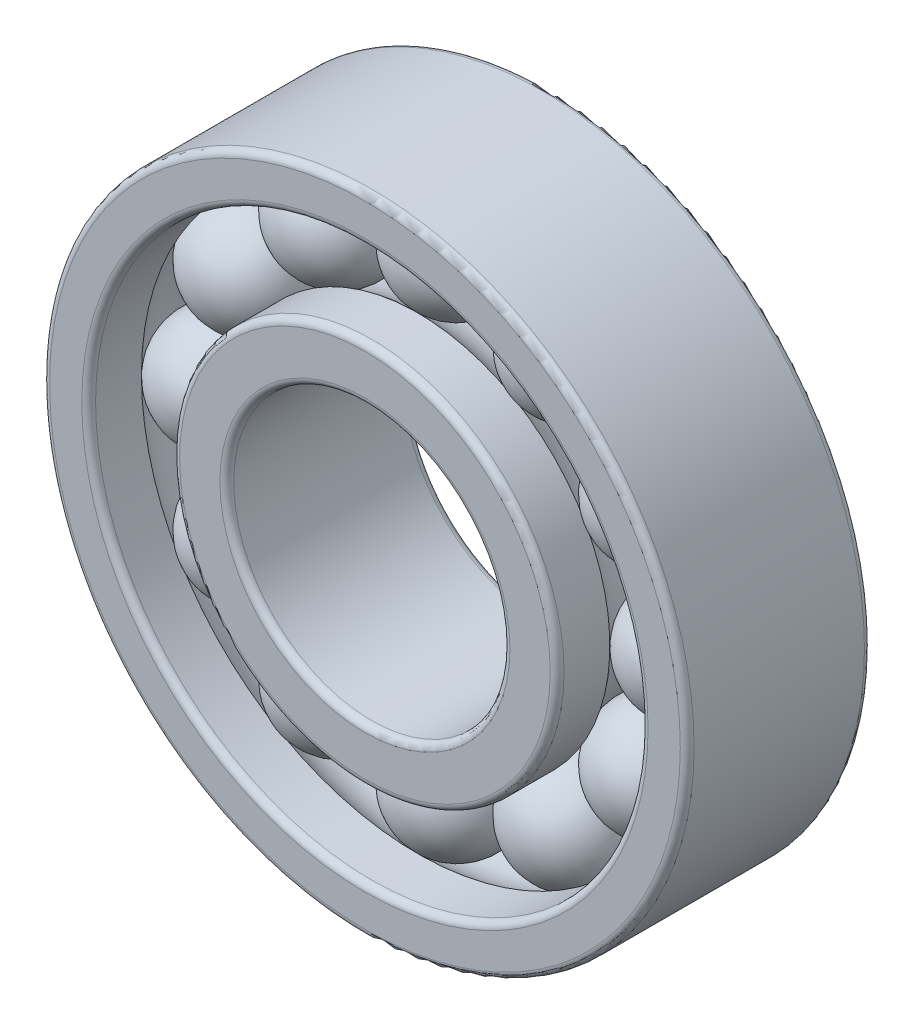
SolidWorks part; units mm, degrees
ref_plane "Front Plane" through (0, 0, 0) normal (0, 0, 1) x (1, 0, 0)
ref_plane "Top Plane" through (0, 0, 0) normal (0, 1, 0) x (1, 0, 0)
ref_plane "Right Plane" through (0, 0, 0) normal (1, 0, 0) x (0, 0, -1)
sketch "Sketch1" plane through (0, 0, 0) normal (0, 0, 1) x (1, 0, 0)
  circle A0 centre (0, 0) radius 14
  circle A1 centre (0, 0) radius 6
  circle A2 centre (0, 0) radius 8.35
  circle A3 centre (0, 0) radius 12
  dimension "D1" = 28
  dimension "D2" = 12
  dimension "D3" = 16.7
  dimension "D4" = 24
extrude "Boss-Extrude1" add sketch "Sketch1" along normal blind 8 contours A0 | A3 | A2 | A1
ref_plane "Middle Plane" through (0, 0, 4) normal (0, 0, 1) x (1, 0, 0)
sketch "Sketch2" plane through (0, 0, 4) normal (0, 0, 1) x (1, 0, 0)
  circle A0 centre (0, 0) radius 10.175
  dimension "D1" = 20.35
sketch "Sketch3" plane through (0, 0, 0) normal (0, 1, 0) x (1, 0, 0)
  line L0 (0, 0) -> (0, -8) construction
  line L1 (-14, -8) -> (14, -8) construction
ref_axis "Axis1" through (0, 0, 0) along (0, 0, 1)
sketch "Sketch4" plane through (0, 0, 0) normal (0, 1, 0) x (1, 0, 0)
  line L0 (0, 0) -> (0, -8) construction
  line L1 (-14, -4) -> (14, -4) construction
  line L2 (-14, 0) -> (-14, -8) construction
  line L3 (14, -8) -> (14, 0) construction
  circle A0 centre (-10.175, -4) radius 2.5
  point P10 (0, -4)
  dimension "D2" = 5
  dimension "D1" = 10.175
sweep "Cut-Sweep1" cut profiles "Sketch4" path "Sketch2"
sketch "Sketch5" plane through (0, 0, 0) normal (0, 1, 0) x (1, 0, 0)
  line L0 (0, 0) -> (0, -8) construction
  line L1 (-14, -4) -> (14, -4) construction
  line L2 (-14, 0) -> (-14, -8) construction
  line L3 (14, -8) -> (14, 0) construction
  line L4 (-10.175, -1.5) -> (-10.175, -6.5)
  arc A0 (-10.175, -1.5) -> (-10.175, -6.5) centre (-10.175, -4) ccw
  point P10 (0, -4)
  dimension "D3" = 2.5
  dimension "D2" = 10.175
revolve "Revolve1" add sketch "Sketch5" angle 360 about L4
pattern_circular "CirPattern1" count 12 over 360 about axis through (0, 0, 8) along (0, 0, -1) reverse direction yes of bodies 105
fillet "Fillet1" radius 0.3 4 edges at (12, 0, 0) (14, 0, 0) (12, 0, 8) (14, 0, 8)
fillet "Fillet2" radius 0.3 4 edges at (6, 0, 8) (8.35, 0, 8) (6, 0, 0) (8.35, 0, 0)
